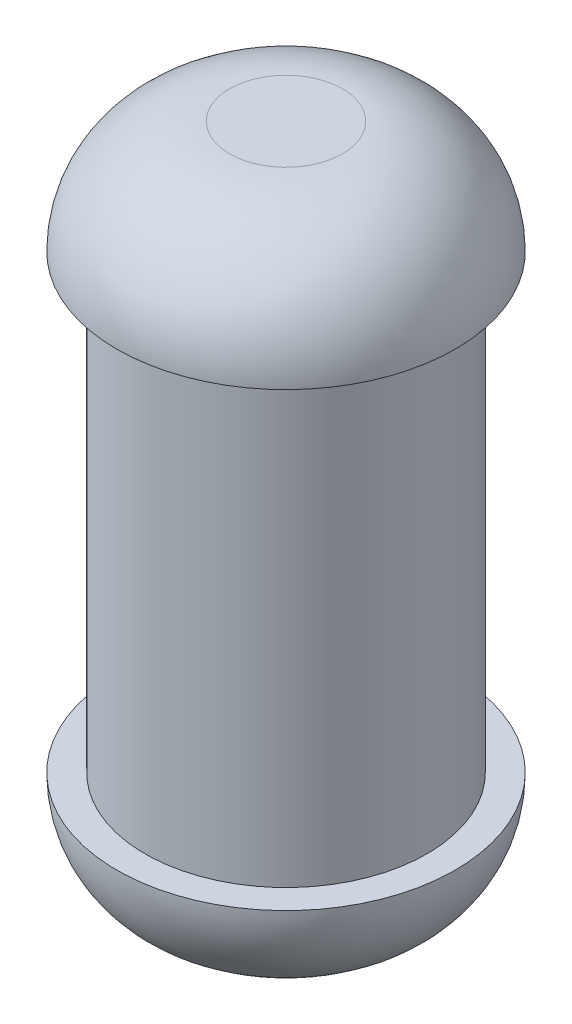
SolidWorks part; units mm, degrees
ref_plane "Front Plane" through (0, 0, 0) normal (0, 0, 1) x (1, 0, 0)
ref_plane "Top Plane" through (0, 0, 0) normal (0, 1, 0) x (1, 0, 0)
ref_plane "Right Plane" through (0, 0, 0) normal (1, 0, 0) x (0, 0, -1)
sketch "Sketch1" plane through (0, 0, 0) normal (0, 1, 0) x (1, 0, 0)
  circle A0 centre (0, 0) radius 3
extrude "Boss-Extrude1" add sketch "Sketch1" along normal blind 2
sketch "Sketch2" plane through (0, 0, 0) normal (0, -1, 0) x (1, 0, 0)
  circle A0 centre (0, 0) radius 2.5
extrude "Boss-Extrude2" add sketch "Sketch2" along normal blind 8
sketch "Sketch3" plane through (0, -8, 0) normal (0, -1, 0) x (1, 0, 0)
  circle A0 centre (0, 0) radius 3
extrude "Boss-Extrude3" add sketch "Sketch3" along normal blind 2
fillet "Fillet1" radius 2 2 edges at (0, 2, 3) (0, -10, -3)
